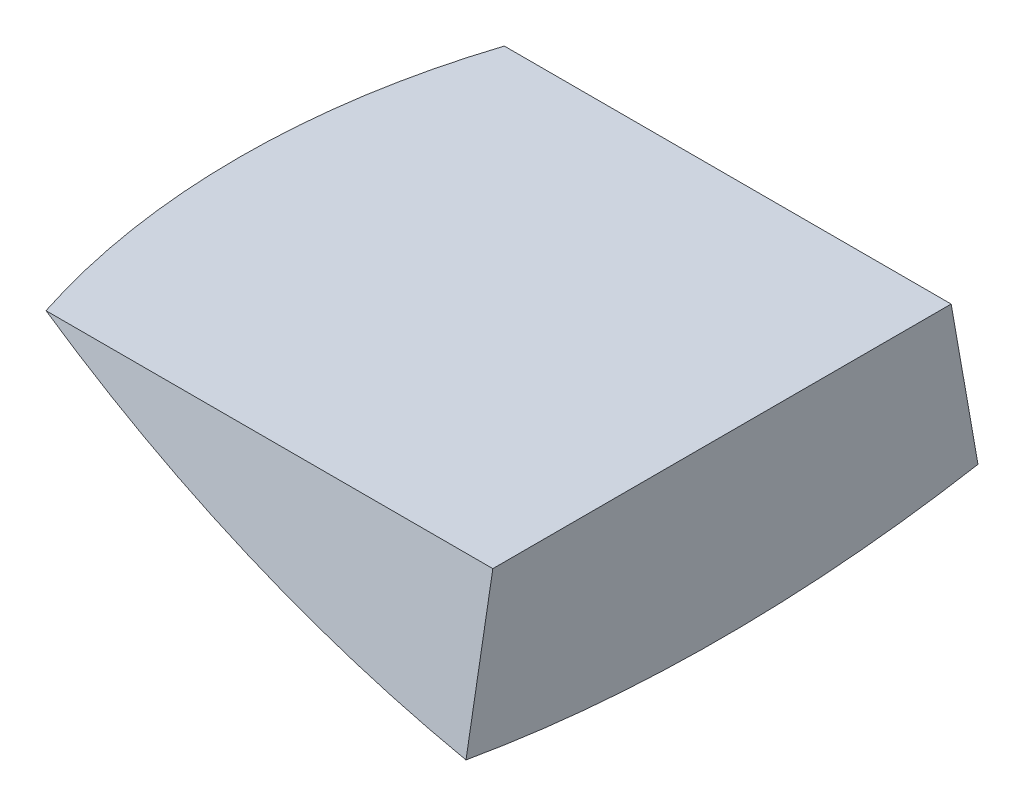
SolidWorks part; units mm, degrees
material "Polyurethane Foam Rigid"
ref_plane "Front Plane" through (0, 0, 0) normal (0, 0, 1) x (1, 0, 0)
ref_plane "Top Plane" through (0, 0, 0) normal (0, 1, 0) x (1, 0, 0)
ref_plane "Right Plane" through (0, 0, 0) normal (1, 0, 0) x (0, 0, -1)
sketch "Sketch1" plane through (0, 0, 0) normal (0, 0, 1) x (1, 0, 0)
  line L0 (-132.3199, -750.4235) -> (-132.3199, -648.8235)
  line L1 (0, 0) -> (0, -17.1989) construction
  line L2 (0, 0) -> (0, -324.9103) construction
  line L3 (0, 0) -> (-132.3199, -750.4235) construction
  line L4 (-132.3199, -648.8235) -> (-399.5899, -648.8235)
  line L5 (0, 0) -> (-376.3803, 0) construction
  arc A0 (-132.3199, -750.4235) -> (-399.5899, -648.8235) centre (0, 0) cw
  dimension "D2" = 762
  dimension "D1" = 10
  dimension "D3" = 101.6
revolve "Revolve1" add sketch "Sketch1" angle 20 mid plane about L5
sketch "Sketch2" plane through (-132.3199, 0, 0) normal (1, 0, 0) x (0, 0, -1)
  line L1 (-217.2973, -505.5801) -> (197.3972, -505.5801)
  line L2 (-217.2973, -505.5801) -> (-217.2973, -661.5235)
  line L3 (-217.2973, -661.5235) -> (197.3972, -661.5235)
  line L4 (197.3972, -505.5801) -> (197.3972, -661.5235)
  arc A1 (-130.3097, -739.0229) -> (130.3097, -739.0229) centre (0, 0) ccw construction
  point P4 (0, -750.4235)
  dimension "D1" = 88.9
extrude "Cut-Extrude1" cut sketch "Sketch2" against normal through all
equation "\"gapAngle\"=10"
equation "\"D1@Sketch1\"=\"gapAngle\""
